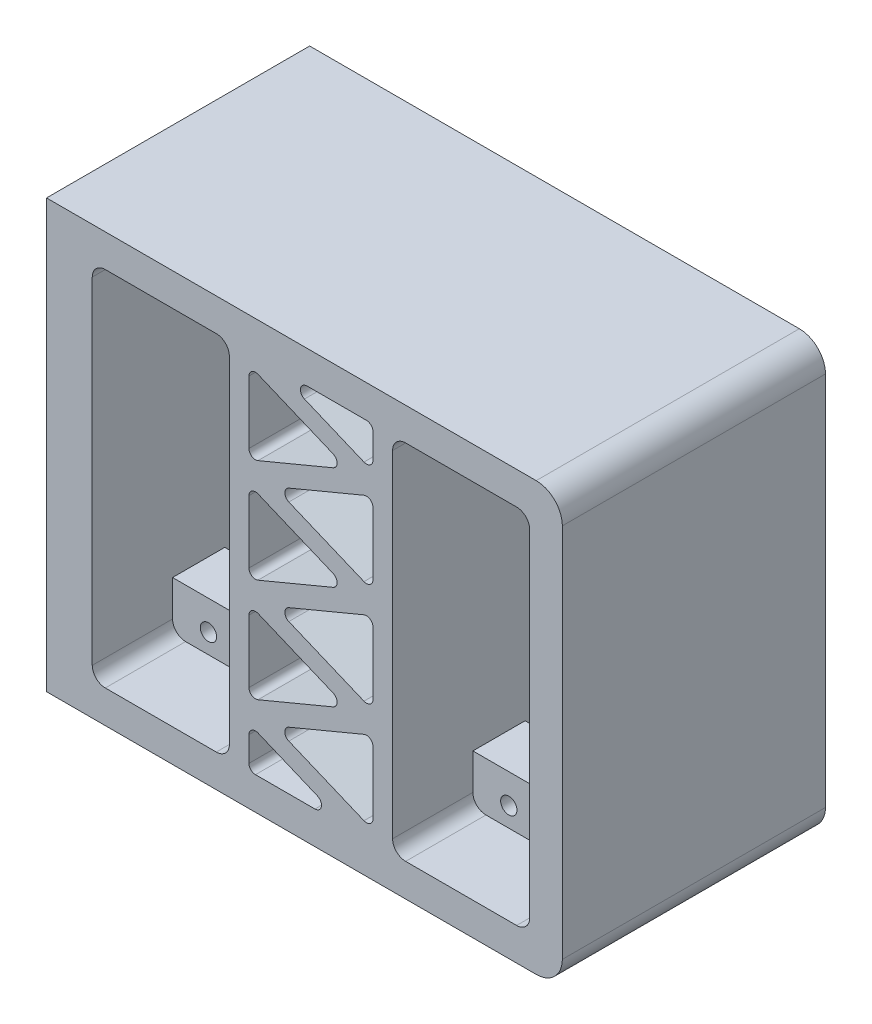
SolidWorks part; units mm, degrees
ref_plane "Front Plane" through (0, 0, 0) normal (0, 0, 1) x (1, 0, 0)
ref_plane "Top Plane" through (0, 0, 0) normal (0, 1, 0) x (1, 0, 0)
ref_plane "Right Plane" through (0, 0, 0) normal (1, 0, 0) x (0, 0, -1)
sketch "Sketch1" plane through (0, 0, 0) normal (0, 0, 1) x (1, 0, 0)
  line L0 (5, 60.5) -> (26, 60.5)
  line L1 (0, 0) -> (77, 0)
  line L2 (0, 0) -> (0, 65.5)
  line L3 (0, 65.5) -> (77, 65.5)
  line L4 (77, 0) -> (77, 65.5)
  line L5 (51, 60.5) -> (72, 60.5)
  line L6 (51, 60.5) -> (51, 5)
  line L7 (51, 5) -> (72, 5)
  line L8 (72, 60.5) -> (72, 5)
  line L9 (5, 60.5) -> (5, 5)
  line L10 (5, 5) -> (26, 5)
  line L12 (26, 60.5) -> (26, 5)
  line L13 (5, 53) -> (26, 53)
  line L14 (51, 53) -> (72, 53)
  line L15 (5, 12.5) -> (26, 12.5)
  line L16 (51, 12.5) -> (72, 12.5)
  line L17 (10.5, 57.5) -> (20.5, 57.5) construction
  line L18 (10.5, 8) -> (20.5, 8) construction
  line L19 (15.5, 57.5) -> (15.5, 8) construction
  line L20 (5, 32.75) -> (26, 32.75) construction
  line L21 (51, 32.75) -> (72, 32.75) construction
  line L22 (61.5, 57.5) -> (61.5, 8) construction
  line L23 (56.5, 57.5) -> (66.5, 57.5) construction
  line L24 (56.5, 8) -> (66.5, 8) construction
  circle A0 centre (10.5, 57.5) radius 1.25
  circle A1 centre (20.5, 57.5) radius 1.25
  circle A2 centre (10.5, 8) radius 1.25
  circle A3 centre (20.5, 8) radius 1.25
  circle A4 centre (56.5, 57.5) radius 1.25
  circle A5 centre (66.5, 57.5) radius 1.25
  circle A6 centre (66.5, 8) radius 1.25
  circle A7 centre (56.5, 8) radius 1.25
  point P33 (15.5, 32.75)
  point P34 (15.5, 32.75)
  point P41 (61.5, 32.75)
  point P42 (61.5, 32.75)
  point P53 (61.5, 8)
  point P55 (61.5, 57.5)
  dimension "D13" = 2.5
  dimension "D1" = 21
  dimension "D2" = 5
  dimension "D3" = 55.5
  dimension "D4" = 55.5
  dimension "D5" = 21
  dimension "D6" = 5
  dimension "D7" = 5
  dimension "D8" = 25
  dimension "D9" = 5
  dimension "D10" = 7.5
  dimension "D11" = 7.5
  dimension "D12" = 10
  dimension "D15" = 49.5
extrude "Boss-Extrude2" add sketch "Sketch1" against normal blind 28 contours L1 L4 L3 L2 L5 L8 L7 L6 L0 L12 L10 L9 | L9 L13 L12 L0 | L15 L9 L10 L12 | L16 L6 L7 L8 | L6 L14 L8 L5 | A0 | A1 | A4 | A5 | A6 | A7 | A3 | A2 region at (15.5, 56.7001, 0) region at (15.5, 8.7999, 0) region at (38.5, 32.75, 0) region at (61.5, 56.7001, 0) region at (61.5, 8.7999, 0) region at (10.5, 57.5, 0) region at (20.5, 57.5, 0) region at (56.5, 57.5, 0) region at (66.5, 57.5, 0) region at (66.5, 8, 0) region at (56.5, 8, 0)
extrude "Boss-Extrude4" add sketch "Sketch1<4>" along normal blind 12.3 contours L1 L4 L3 L2 L5 L8 L7 L6 L0 L12 L10 L9 region at (38.5, 32.75, 0)
sketch "Sketch1<4>" plane through (0, 0, 0) normal (0, 0, 1) x (1, 0, 0) same geometry as "Sketch1"
extrude "Cut-Extrude1" cut sketch "Sketch1<5>" against normal blind 12 contours A0 | A2 | A3 | A7 | A6 | A4 | A1 | A5 region at (10.5, 57.5, 0) region at (10.5, 8, 0) region at (20.5, 8, 0) region at (56.5, 57.5, 0) region at (66.5, 8, 0) region at (56.5, 8, 0)
sketch "Sketch1<5>" plane through (0, 0, 0) normal (0, 0, 1) x (1, 0, 0) same geometry as "Sketch1"
sketch "Sketch5" plane through (0, 0, 12.3) normal (0, 0, 1) x (1, 0, 0)
  line L0 (28.4223, 59.1157) -> (44.105, 52.5714)
  line L1 (26, 5) -> (51, 5)
  line L2 (26, 5) -> (26, 60.5)
  line L3 (26, 60.5) -> (51, 60.5)
  line L4 (51, 5) -> (51, 60.5)
  line L5 (26, 60.5) -> (26, 5) construction
  line L6 (51, 60.5) -> (51, 5) construction
  line L7 (5, 60.5) -> (26, 60.5) construction
  line L8 (5, 5) -> (26, 5) construction
  line L9 (29, 60.5) -> (48, 60.5)
  line L10 (48, 5) -> (48, 60.5)
  line L11 (29, 5) -> (48, 5)
  line L12 (29, 5) -> (29, 60.5)
  line L13 (29, 60.5) -> (48, 52.5714)
  line L14 (48, 52.5714) -> (29, 44.6429)
  line L15 (29, 44.6429) -> (48, 36.7143)
  line L16 (48, 36.7143) -> (29, 28.7857)
  line L17 (29, 28.7857) -> (48, 20.8571)
  line L18 (48, 20.8571) -> (29, 12.9286)
  line L19 (29, 12.9286) -> (48, 5)
  line L20 (44.105, 52.5714) -> (25.105, 44.6429)
  line L21 (25.105, 44.6429) -> (44.105, 36.7143)
  line L22 (44.105, 36.7143) -> (25.105, 28.7857)
  line L23 (25.105, 28.7857) -> (44.105, 20.8571)
  line L24 (44.105, 20.8571) -> (25.105, 12.9286)
  line L25 (25.105, 12.9286) -> (47.4223, 3.6157)
  line L26 (29.5777, 61.8843) -> (51.895, 52.5714)
  line L27 (51.895, 52.5714) -> (32.895, 44.6429)
  line L28 (32.895, 44.6429) -> (51.895, 36.7143)
  line L29 (51.895, 36.7143) -> (32.895, 28.7857)
  line L30 (32.895, 28.7857) -> (51.895, 20.8571)
  line L31 (51.895, 20.8571) -> (32.895, 12.9286)
  line L32 (32.895, 12.9286) -> (48.5777, 6.3843)
  dimension "D2" = 1.5
  dimension "D1" = 3
  dimension "D4" = 3
  dimension "D3" = 1.5
extrude "Cut-Extrude2" cut sketch "Sketch5" against normal through all contours L20 L0 L12 | L9 L26 L10 | L27 L28 L10 | L22 L21 L12 | L29 L30 L10 | L24 L23 L12 | L31 L32 L10 | L25 L12 L11 region at (34.035, 52.5714, 12.3) region at (42.965, 58.3989, 12.3) region at (34.035, 36.7143, 12.3) region at (42.965, 44.6429, 12.3) region at (42.965, 28.7857, 12.3) region at (34.035, 20.8571, 12.3) region at (42.965, 12.9286, 12.3) region at (34.035, 7.1011, 12.3)
fillet "Fillet4" radius 1 24 edges at (44.105, 5, -7.85) (29, 11.3032, -7.85) (29, 5, -7.85) (48, 6.6254, -7.85) (48, 19.2318, -7.85) (32.895, 12.9286, -7.85) (29, 14.5539, -7.85) (29, 27.1604, -7.85) (44.105, 20.8571, -7.85) (48, 22.4825, -7.85) (48, 35.0889, -7.85) (32.895, 28.7857, -7.85) (44.105, 36.7143, -7.85) (29, 30.4111, -7.85) (29, 43.0175, -7.85) (48, 38.3396, -7.85) (32.895, 44.6429, -7.85) (48, 50.9461, -7.85) (29, 46.2682, -7.85) (44.105, 52.5714, -7.85) (29, 58.8746, -7.85) (48, 54.1968, -7.85) (48, 60.5, -7.85) (32.895, 60.5, -7.85)
sketch "Sketch8" plane through (0, 12.5, 0) normal (0, 1, 0) x (1, 0, 0)
  line L0 (26, 28) -> (26, 0) construction
  line L1 (5, 28) -> (26, 28)
  line L2 (5, 28) -> (5, 8)
  line L3 (5, 8) -> (26, 8)
  line L4 (26, 28) -> (26, 8)
  line L5 (51, 0) -> (72, 0) construction
  line L6 (51, 28) -> (67, 28)
  line L7 (51, 28) -> (51, 8)
  line L8 (51, 8) -> (67, 8)
  line L9 (67, 28) -> (67, 8)
  dimension "D1" = 8
extrude "Cut-Extrude8" cut sketch "Sketch8" against normal blind 10
ref_plane "Midplane" through (0, 32.75, 0) normal (0, 1, 0) x (1, 0, 0)
ref_plane "Plane2" through (61.5, 0, 0) normal (1, 0, 0) x (0, 0, -1)
ref_plane "Plane3" through (15.5, 0, 0) normal (1, 0, 0) x (0, 0, -1)
sketch "Sketch10" plane through (61.5, 0, 0) normal (1, 0, 0) x (0, 0, -1)
  line L0 (28, 2.5) -> (8, 2.5) construction
  line L1 (8, 2.5) -> (8, 12.5) construction
  line L2 (28, 2.5) -> (8, 2.5)
  line L3 (8, 2.5) -> (8, 12.5)
  line L4 (8, 12.5) -> (18, 2.5)
  dimension "D1" = 45
extrude "Boss-Extrude5" add sketch "Sketch10" along normal blind 1.5 and the other way blind 1.5 contours L4 L3 L2 region at (61.5, 5.8333, -11.3333)
sketch "Sketch11" plane through (15.5, 0, 0) normal (1, 0, 0) x (0, 0, -1)
  line L0 (28, 2.5) -> (8, 2.5) construction
  line L1 (8, 2.5) -> (8, 12.5) construction
  line L2 (28, 2.5) -> (8, 2.5)
  line L3 (8, 2.5) -> (8, 12.5)
  line L4 (8, 12.5) -> (18, 2.5)
  dimension "D1" = 45
extrude "Boss-Extrude6" add sketch "Sketch11" along normal blind 1.5 and the other way blind 1.5 contours L4 L3 L2 region at (15.5, 5.8333, -11.3333)
mirror "Mirror2" about plane through (0, 32.75, 0) normal (0, 1, 0) of "Boss-Extrude6", "Boss-Extrude5", "Cut-Extrude8"
sketch "Sketch13" plane through (0, 0, 0) normal (-1, 0, 0) x (0, 0, 1)
  line L4 (-28, 0) -> (12.3, 0)
  line L5 (12.3, 0) -> (12.3, 65.5)
  line L6 (12.3, 65.5) -> (-28, 65.5)
  line L7 (-28, 65.5) -> (-28, 0)
  line L8 (-28, 0) -> (12.3, 0)
  line L9 (12.3, 0) -> (12.3, 65.5)
  line L10 (12.3, 65.5) -> (-28, 65.5)
  line L11 (-28, 65.5) -> (-28, 0)
  dimension "D1" = 0
extrude "Boss-Extrude7" add sketch "Sketch13" along normal blind 2
fillet "Fillet3" radius 2 16 edges at (51, 60.5, 6.15) (72, 5, 6.15) (72, 60.5, 6.15) (51, 5, 6.15) (5, 5, 6.15) (26, 5, 6.15) (26, 60.5, 6.15) (5, 60.5, 6.15) (67, 63, -18) (67, 2.5, -18) (51, 2.5, -18) (51, 63, -18) (26, 63, -18) (26, 2.5, -18) (5, 63, -18) (5, 2.5, -18)
sketch "Sketch14" plane through (-2, 0, 0) normal (-1, 0, 0) x (0, 0, 1)
  line L8 (-24, 61.5) -> (-24, 4)
  line L9 (-24, 4) -> (8.3, 4)
  line L10 (8.3, 4) -> (8.3, 61.5)
  line L11 (8.3, 61.5) -> (-24, 61.5)
  line L12 (-24, 61.5) -> (-24, 4) construction
  line L13 (-24, 4) -> (8.3, 4) construction
  line L14 (8.3, 4) -> (8.3, 61.5) construction
  line L15 (8.3, 61.5) -> (-24, 61.5) construction
  circle A0 centre (-24, 61.5) radius 1.25
  circle A1 centre (8.3, 61.5) radius 1.25
  circle A2 centre (8.3, 4) radius 1.25
  circle A3 centre (-24, 4) radius 1.25
  dimension "D2" = 2.5
  dimension "D1" = 4
extrude "Cut-Extrude9" cut sketch "Sketch14" against normal blind 7
fillet "Fillet7" radius 4 2 edges at (77, 65.5, -7.85) (77, 0, -7.85)
